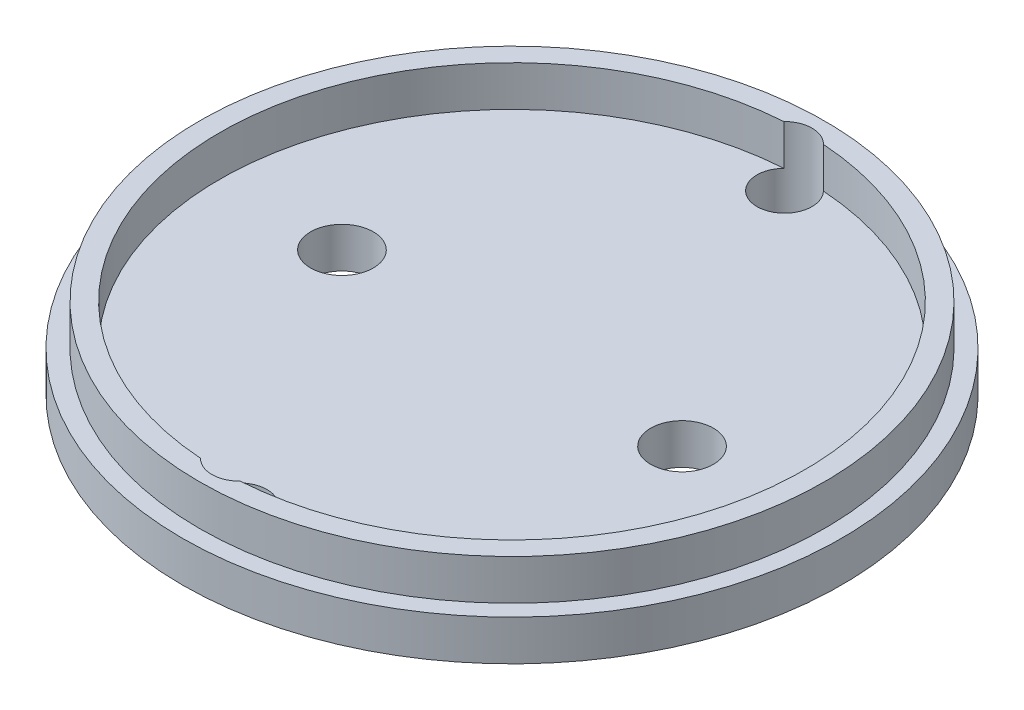
SolidWorks part; units mm, degrees
ref_plane "Front Plane" through (0, 0, 0) normal (0, 0, 1) x (1, 0, 0)
ref_plane "Top Plane" through (0, 0, 0) normal (0, 1, 0) x (1, 0, 0)
ref_plane "Right Plane" through (0, 0, 0) normal (1, 0, 0) x (0, 0, -1)
sketch "Sketch1" plane through (0, 0, 0) normal (0, 1, 0) x (1, 0, 0)
  circle A0 centre (0, 0) radius 40.7
  circle A1 centre (0, 0) radius 38.6
  circle A2 centre (0, 0) radius 36.1
  dimension "D1" = 81.4
  dimension "D2" = 77.2
  dimension "D3" = 2.5
extrude "Boss-Extrude1" add sketch "Sketch1" along normal blind 5 contours A1 A2 region at (-37.5082, 0, 0)
extrude "Boss-Extrude2" add sketch "Sketch1<4>" against normal blind 5 contours A1 A2 | A2 | A0 A1 region at (-39.5488, 0, 0) region at (-37.5082, 0, 0) region at (0, 0, 0)
sketch "Sketch1<4>" plane through (0, 0, 0) normal (0, 1, 0) x (1, 0, 0) same geometry as "Sketch1"
sketch "Sketch4" plane through (0, -5, 0) normal (0, -1, 0) x (1, 0, 0)
  line L0 (21, 0) -> (-21, 0) construction
  line L1 (0, 33.655) -> (0, -33.655) construction
  circle A0 centre (-21, 0) radius 3.875
  circle A1 centre (21, 0) radius 3.875
  circle A2 centre (0, 33.655) radius 3.4
  circle A3 centre (0, -33.655) radius 3.4
  point P5 (0, 0)
  point P11 (0, 0)
  point P13 (0, 0)
  point P14 (0, 0)
  point P15 (0, 15.1463)
  dimension "D2" = 7.75
  dimension "D4" = 6.8
  dimension "D1" = 42
  dimension "D3" = 67.31
extrude "Cut-Extrude1" cut sketch "Sketch4" against normal through all both and the other way through all
